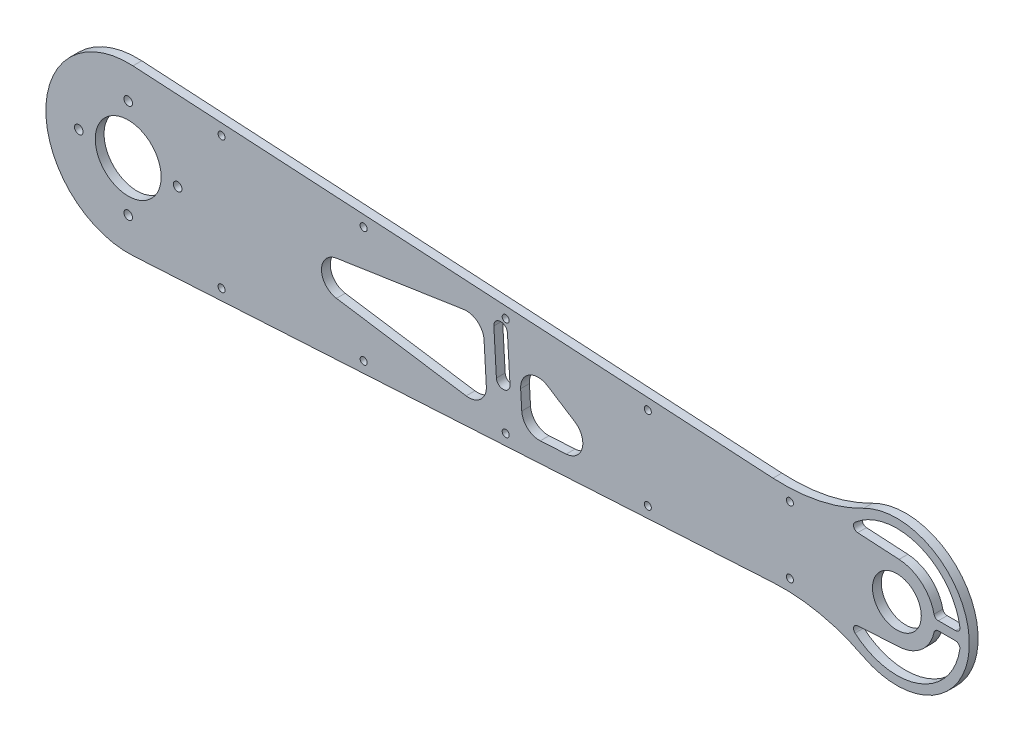
SolidWorks part; units mm, degrees
material "Thornel VCB-20 Carbon Cloth"
ref_plane "Front Plane" through (0, 0, 0) normal (0, 0, 1) x (1, 0, 0)
ref_plane "Top Plane" through (0, 0, 0) normal (0, 1, 0) x (1, 0, 0)
ref_plane "Right Plane" through (0, 0, 0) normal (1, 0, 0) x (0, 0, -1)
sketch "Sketch1" plane through (0, 0, 0) normal (0, 0, 1) x (1, 0, 0)
  line L0 (-175, 0) -> (175, 0) construction
  line L1 (-172.8341, 37.4374) -> (175.9983, 17.2563)
  line L2 (-172.8341, -37.4374) -> (175.9983, -17.2563)
  line L3 (126.2798, 15.1243) -> (-132.5, 30.0956) construction
  line L4 (-67.8051, -26.3528) -> (-3.1101, -22.6099) construction
  line L5 (-137.5, 0) -> (-137.5, 62.9978) construction
  line L6 (139.694, 0) -> (139.694, 19.7682) construction
  circle A0 centre (175, 0) radius 11.1125
  arc A1 (175.9983, 17.2563) -> (175.9983, -17.2563) centre (175, 0) cw
  circle A3 centre (-175, 0) radius 22.5 construction
  circle A7 centre (-175, 0) radius 15
  circle A8 centre (175, 0) radius 35.306 construction
  circle A9 centre (-132.5, 30.0956) radius 1.6
  circle A10 centre (-67.8051, 26.3528) radius 1.6
  circle A11 centre (-3.1101, 22.6099) radius 1.6
  circle A12 centre (61.5848, 18.8671) radius 1.6
  circle A13 centre (126.2798, 15.1243) radius 1.6
  circle A15 centre (126.2798, -15.1243) radius 1.6
  circle A16 centre (61.5848, -18.8671) radius 1.6
  circle A17 centre (-3.1101, -22.6099) radius 1.6
  circle A18 centre (-67.8051, -26.3528) radius 1.6
  circle A19 centre (-132.5, -30.0956) radius 1.6
  arc A20 (-172.8341, 37.4374) -> (-172.8341, -37.4374) centre (-175, 0) ccw
  point P4 (0, 0)
  point P14 (183.1044, 15.5828)
  point P15 (0, 0)
  point P17 (0, 0)
  point P18 (-175, 22.5)
  point P21 (-197.5, 0)
  point P22 (-175, -22.5)
  point P23 (-152.5, 0)
  point P29 (0, 0)
  point P30 (184.4151, 15.0665)
  point P37 (187.7845, 15.3121)
  point P41 (191.0298, 15.1243)
  point P42 (195.944, 19.7682)
  point P56 (0, 0)
  point P57 (-311.77, 0)
  point P58 (0, 0)
  point P59 (0, 0)
  dimension "D2" = 22.225
  dimension "D3" = 37.5
  dimension "D5" = 45
  dimension "D6" = 3.2
  dimension "D7" = 259.2125
  dimension "D8" = 5
  dimension "D10" = 30
  dimension "D11" = 70.612
  dimension "D16" = 5
  dimension "D1" = 350
  dimension "D12" = 5
extrude "Boss-Extrude1" add sketch "Sketch1" along normal blind 4
sketch "Sketch4" plane through (0, 0, 4) normal (0, 0, 1) x (1, 0, 0)
  point P10 (-197.5, 0)
  point P13 (-175, 22.5)
  point P16 (-152.5, 0)
  point P19 (-175, -22.5)
  point P30 (0, 0)
  point P31 (0, 0)
hole_wizard "M3.5 Clearance Hole1" positions "Sketch4" profile "Sketch6" hole size "M3.5" standard "ANSI Metric" end condition up to next
sketch "Sketch6" plane through (-197.5, 0, 4) normal (1, 0, 0) x (0, -1, 0)
  line L0 (0, 0) -> (0, 4)
  line L1 (0, 4) -> (1.95, 4)
  line L2 (1.95, 4) -> (1.95, 0)
  line L5 (1.95, 0) -> (0, 0)
  line L11 (0, -6.35) -> (0, 107.95) construction
  dimension "Thru Hole Dia." = 3.9
  dimension "Thru Hole Depth" = 4
sketch "Sketch7" plane through (0, 0, 4) normal (0, 0, 1) x (1, 0, 0)
  line L0 (61.5848, 18.8671) -> (61.5848, -18.8671) construction
  line L1 (61.5848, -18.8671) -> (126.2798, 0) construction
  line L2 (126.2798, 0) -> (61.5848, 18.8671) construction
  line L3 (126.2798, 0) -> (-152.5, 0) construction
  line L4 (126.2798, -15.1243) -> (126.2798, 15.1243) construction
  line L5 (49.9706, 19.1292) -> (89.2295, 7.6801)
  line L6 (89.2295, -7.6801) -> (49.9706, -19.1292)
  line L7 (39.7309, -11.4492) -> (39.7309, 11.4492)
  line L8 (-3.1101, -22.6099) -> (-6.0257, 27.787) construction
  line L9 (-3.1101, 22.6099) -> (61.5848, -18.8671) construction
  line L10 (-3.1101, 22.6099) -> (61.5848, 18.8671) construction
  line L11 (-3.1101, -22.6099) -> (61.5848, -18.8671) construction
  line L12 (-152.5, 0) -> (-67.8051, 26.3528) construction
  line L13 (-67.8051, 26.3528) -> (-3.1101, 22.6099) construction
  line L14 (-3.1101, 22.6099) -> (-152.5, 0) construction
  line L15 (83.4388, -13.4947) -> (83.4388, 6.0456)
  line L16 (75.9008, 14.0322) -> (42.3992, 15.9704)
  line L17 (37.6194, 1.249) -> (71.121, -20.2295)
  line L18 (15.9913, 5.6122) -> (28.3123, -2.287)
  line L19 (24.4566, -17.0084) -> (12.6321, -17.6925)
  line L20 (4.1834, -10.1679) -> (3.6869, -1.5846)
  line L21 (175.9983, 17.2563) -> (-172.8341, 37.4374) construction
  line L22 (-172.8341, -37.4374) -> (175.9983, -17.2563) construction
  line L23 (-11.9411, -8.4773) -> (-12.9665, 9.2462)
  line L24 (-22.1503, 16.6941) -> (-80.1895, 7.9099)
  line L25 (-80.1895, -7.9099) -> (-21.1249, -16.8493)
  line L35 (-197.5, 0) -> (-67.8051, 26.3528) construction
  line L52 (-67.8051, -26.3528) -> (-175, -22.5) construction
  line L53 (-13.662, -33.302) -> (-67.7503, -31.358) construction
  line L54 (1.0099, -23.8229) -> (38.9341, -25.1859) construction
  line L55 (-4.2593, -2.7465) -> (-5.4144, 17.2201) construction
  line L56 (-7.3541, -2.9255) -> (-8.5092, 17.0411)
  line L57 (-1.1645, -2.5674) -> (-2.3196, 17.3992)
  arc A0 (89.2295, 7.6801) -> (89.2295, -7.6801) centre (86.9898, 0) cw
  arc A1 (49.9706, -19.1292) -> (39.7309, -11.4492) centre (47.7309, -11.4492) cw
  arc A2 (49.9706, 19.1292) -> (39.7309, 11.4492) centre (47.7309, 11.4492) ccw
  arc A3 (83.4388, 6.0456) -> (75.9008, 14.0322) centre (75.4388, 6.0456) ccw
  arc A4 (42.3992, 15.9704) -> (37.6194, 1.249) centre (41.9372, 7.9837) ccw
  arc A5 (83.4388, -13.4947) -> (71.121, -20.2295) centre (75.4388, -13.4947) cw
  arc A6 (28.3123, -2.287) -> (24.4566, -17.0084) centre (23.9946, -9.0218) cw
  arc A7 (12.6321, -17.6925) -> (4.1834, -10.1679) centre (12.1701, -9.7059) cw
  arc A8 (15.9913, 5.6122) -> (3.6869, -1.5846) centre (11.6735, -1.1225) ccw
  arc A9 (-11.9411, -8.4773) -> (-21.1249, -16.8493) centre (-19.9278, -8.9393) cw
  arc A10 (-12.9665, 9.2462) -> (-22.1503, 16.6941) centre (-20.9531, 8.7842) ccw
  arc A11 (-80.1895, 7.9099) -> (-80.1895, -7.9099) centre (-78.9924, 0) ccw
  circle A30 centre (-175, 0) radius 15 construction
  circle A31 centre (-175, 0) radius 15 construction
  circle A32 centre (-175, 0) radius 22.5 construction
  circle A49 centre (-3.1101, -22.6099) radius 1.6 construction
  circle A50 centre (-3.1101, -22.6099) radius 1.6
  arc A56 (-7.3541, -2.9255) -> (-1.1645, -2.5674) centre (-4.2593, -2.7465) ccw
  arc A57 (-2.3196, 17.3992) -> (-8.5092, 17.0411) centre (-5.4144, 17.2201) ccw
  point P36 (115.5643, 0)
  point P59 (-132.4525, 0)
  point P102 (-13.662, -33.302)
  point P126 (-4.8369, 7.2368)
  dimension "D8" = 8
  dimension "D12" = 5
  dimension "D20" = 3.1
  dimension "D1" = 3
  dimension "D3" = 8
  dimension "D4" = 8
  dimension "D5" = 8
  dimension "D6" = 16
  dimension "D7" = 6
  dimension "D14" = 5
  dimension "D16" = 24.8967
  dimension "D22" = 20
extrude "Cut-Extrude1" cut sketch "Sketch7" against normal blind 10 contours L57 A57 L56 A56 | L24 A11 L25 A9 L23 A10 | L18 A8 L20 A7 L19 A6 region at (16.5163, -6.5396, 4) region at (-44.307, -0.0844, 4) region at (-4.8369, 7.2368, 4)
sketch "Sketch9" plane through (0, 0, 4) normal (0, 0, 1) x (1, 0, 0)
  line L2 (175.9983, 17.2563) -> (-172.8341, 37.4374) construction
  line L3 (-172.8341, -37.4374) -> (175.9983, -17.2563) construction
  line L4 (254.5375, 0) -> (208, 0) construction
  line L5 (192.169, 2) -> (203.931, 2)
  line L6 (192.169, -2) -> (203.931, -2)
  line L7 (152.7515, 18.6012) -> (147.9343, 18.8799)
  line L8 (152.7515, -18.6012) -> (147.9343, -18.8799)
  arc A1 (147.9343, -18.8799) -> (147.9343, 18.8799) centre (175, 0) ccw
  arc A2 (175.9983, -17.2563) -> (175.9983, 17.2563) centre (175, 0) ccw construction
  arc A3 (192.169, -2) -> (192.169, 2) centre (175, 0) ccw
  arc A4 (152.7515, 18.6012) -> (203.931, 2) centre (175, 0) cw
  arc A5 (203.931, -2) -> (152.7515, -18.6012) centre (175, 0) cw
  dimension "D1" = 33
  dimension "D2" = 4
  dimension "D3" = 4
extrude "Boss-Extrude2" add sketch "Sketch9" against normal up to surface (4 mm away) up to face at (-38.6209, 0.0755, 0)
fillet "Fillet1" radius 2 6 edges at (152.7515, -18.6012, 2) (192.169, -2, 2) (203.931, -2, 2) (192.169, 2, 2) (203.931, 2, 2) (152.7515, 18.6012, 2)
fillet "Fillet2" radius 80 2 edges at (147.9343, 18.8799, 2) (147.9343, -18.8799, 2)
